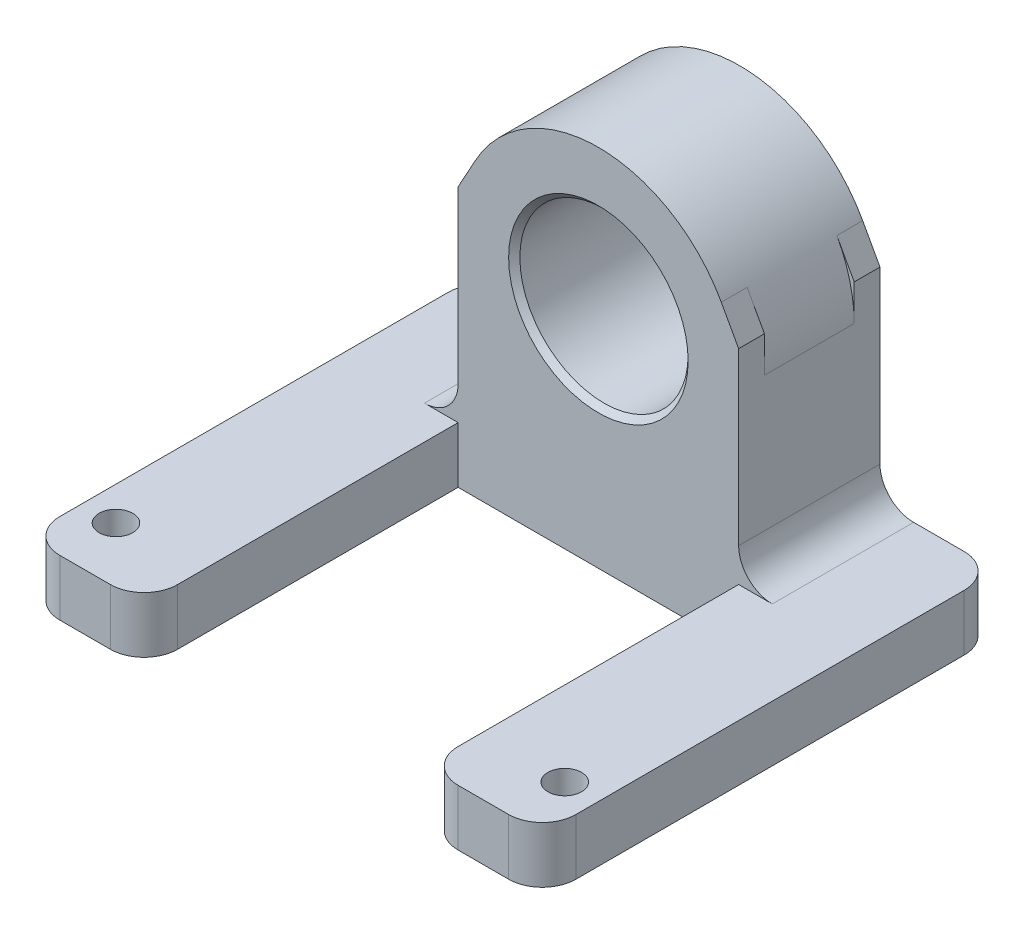
SolidWorks part; units mm, degrees
material "ABS"
ref_plane "前视基准面" through (0, 0, 0) normal (0, 0, 1) x (1, 0, 0)
ref_plane "上视基准面" through (0, 0, 0) normal (0, 1, 0) x (1, 0, 0)
ref_plane "右视基准面" through (0, 0, 0) normal (1, 0, 0) x (0, 0, -1)
sketch "草图1" plane through (0, 0, 0) normal (0, 0, 1) x (1, 0, 0)
  line L0 (0, 0) -> (0, -20) construction
  line L1 (-22.5, -20) -> (22.5, -20)
  line L2 (22.5, -20) -> (22.5, -15)
  line L3 (22.5, -15) -> (10.9562, 6.0176)
  line L4 (-22.5, -20) -> (-22.5, -15)
  line L5 (-22.5, -15) -> (-10.9562, 6.0176)
  circle A0 centre (0, 0) radius 7.5
  arc A1 (10.9562, 6.0176) -> (-10.9562, 6.0176) centre (0, 0) ccw
  dimension "D1" = 15
  dimension "D2" = 25
  dimension "D3" = 20
  dimension "D4" = 45
  dimension "D5" = 5
extrude "凸台-拉伸1" add sketch "草图1" along normal mid plane 12.6
sketch "草图2" plane through (0, 0, 0) normal (0, 0, 1) x (1, 0, 0)
  line L0 (0, 0) -> (0, -20) construction
  line L1 (-22.5, -20) -> (22.5, -20) construction
  line L2 (22.5, -15) -> (12.5, -15)
  line L3 (12.5, -15) -> (12.5, 0)
  line L4 (-22.5, -15) -> (-12.5, -15)
  line L5 (-12.5, -15) -> (-12.5, 0)
  line L6 (-10.9562, 6.0176) -> (-22.5, -15) construction
  line L7 (22.5, -15) -> (10.9562, 6.0176) construction
  line L8 (-10.9562, 6.0176) -> (-22.5, -15)
  line L9 (22.5, -15) -> (10.9562, 6.0176)
  arc A0 (-10.9562, 6.0176) -> (-12.5, 0) centre (0, 0) ccw
  arc A2 (12.5, 0) -> (10.9562, 6.0176) centre (0, 0) ccw
extrude "切除-拉伸1" cut sketch "草图2" against normal mid plane 8
sketch "草图3" plane through (0, -20, 0) normal (0, -1, 0) x (1, 0, 0)
  line L0 (0, 6.3) -> (0, 0) construction
  line L1 (-22.5, 6.3) -> (22.5, 6.3) construction
  line L2 (0, 0) -> (17.5, 0) construction
  line L7 (22.5, 4) -> (12.5, 4)
  line L8 (22.5, -4) -> (22.5, 4)
  line L9 (12.5, -4) -> (22.5, -4)
  line L10 (12.5, 4) -> (12.5, -4)
  line L11 (22.5, 4) -> (12.5, 4) construction
  line L12 (22.5, -4) -> (22.5, 4) construction
  line L13 (12.5, -4) -> (22.5, -4) construction
  line L14 (12.5, 4) -> (12.5, -4) construction
  circle A0 centre (17.5, 0) radius 2
  circle A1 centre (-17.5, 0) radius 2
  dimension "D1" = 4
  dimension "D3" = 35
  dimension "D2" = 0
extrude "切除-拉伸2" cut sketch "草图3" against normal through all
chamfer "倒角1" distance 0.5 angle 45 2 edges at (7.5, 0, -6.3) (7.5, 0, 6.3)
ref_plane "基准面1" through (0, 0, 6.3) normal (0, 0, 1) x (1, 0, 0)
sketch "草图4" plane through (0, 0, 6.3) normal (0, 0, 1) x (1, 0, 0)
  line L0 (0, 0) -> (0, -50000) construction
  line L1 (-22.5, -15) -> (-23, -15)
  line L2 (-22.5, -20) -> (-23, -20)
  line L3 (-23, -20) -> (-23, -15)
  line L4 (-22.5, -15) -> (23, -15)
  line L5 (23, -15) -> (23, -20)
  line L6 (23, -20) -> (-22.5, -20)
  dimension "D1" = 23
  dimension "D2" = 23
extrude "凸台-拉伸2" add sketch "草图4" along normal blind 28 and the other way blind 12.6
sketch "草图5" plane through (0, 0, 0) normal (0, 1, 0) x (1, 0, 0)
  line L0 (0, 0) -> (0, -50000) construction
  line L1 (-17.875, -6.3) -> (17.875, -6.3) construction
  circle A0 centre (-20, -29.3) radius 1.5
  circle A1 centre (20, -29.3) radius 1.5
  dimension "D1" = 3
  dimension "D2" = 20
  dimension "D3" = 23
extrude "切除-拉伸3" cut sketch "草图5" against normal through all
sketch "草图6" plane through (0, 0, 0) normal (0, 1, 0) x (1, 0, 0)
  line L0 (-12.5, -6.3) -> (-12.5, -34.3)
  line L1 (23, -34.3) -> (-23, -34.3) construction
  line L2 (12.5, -6.3) -> (12.5, -34.3)
  line L3 (12.5, -34.3) -> (-12.5, -34.3)
  line L4 (-12.5, -6.3) -> (12.5, -6.3)
  line L5 (-17.875, -6.3) -> (17.875, -6.3) construction
extrude "切除-拉伸4" cut sketch "草图6" against normal through all
sketch "草图7" plane through (0, 0, 6.3) normal (0, 0, 1) x (1, 0, 0)
  line L0 (-12.5, -15) -> (-12.5, 7.3591)
  line L1 (-12.5, 7.3591) -> (-22.5, 7.3591)
  line L2 (-22.5, 7.3591) -> (-22.5, -15)
  line L3 (-22.5, -15) -> (-12.5, -15)
  line L4 (12.5, -15) -> (12.5, 8.0323)
  line L5 (12.5, 8.0323) -> (23, 8.0323)
  line L6 (23, 8.0323) -> (23, -15)
  line L7 (23, -15) -> (12.5, -15)
extrude "切除-拉伸5" cut sketch "草图7" against normal through all
fillet "圆角1" radius 3 8 edges at (23, -17.5, -6.3) (-23, -17.5, -6.3) (-23, -17.5, 34.3) (-12.5, -17.5, 34.3) (12.5, -17.5, 34.3) (23, -17.5, 34.3) (-12.5, -15, 0) (12.5, -15, 0)
